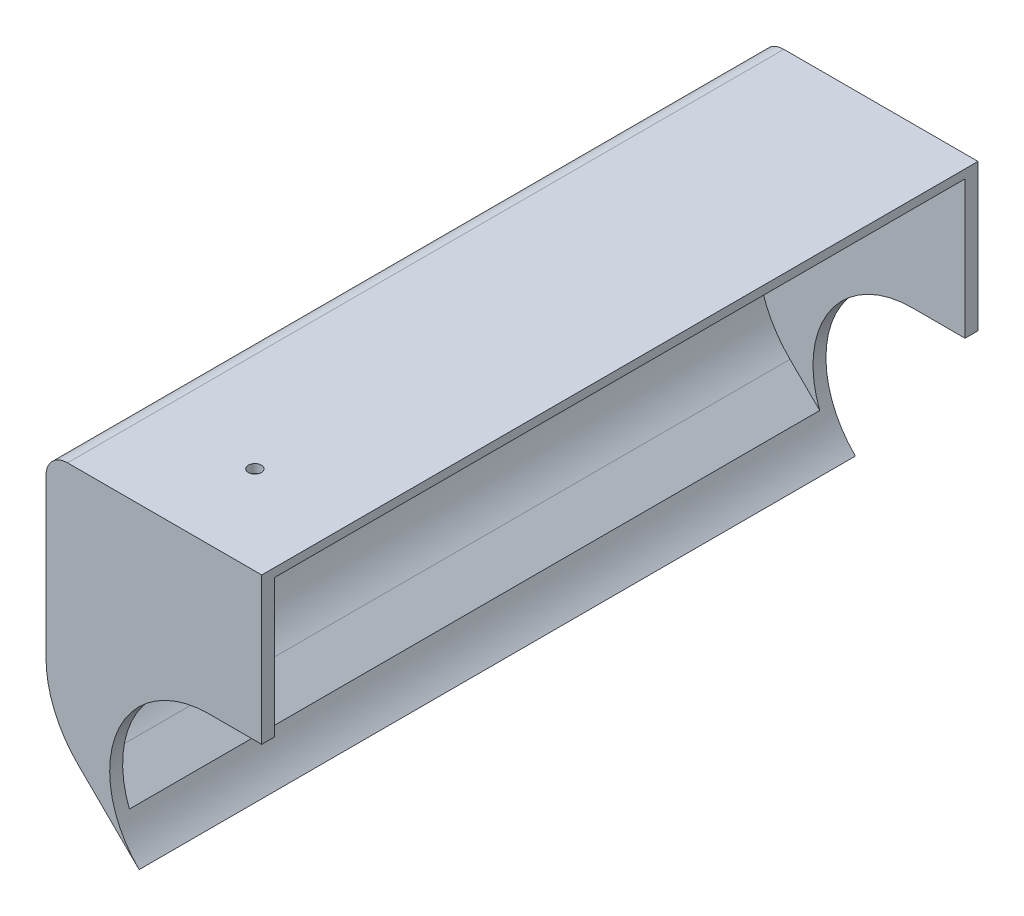
SolidWorks part; units mm, degrees
ref_plane "Front Plane" through (0, 0, 0) normal (0, 0, 1) x (1, 0, 0)
ref_plane "Top Plane" through (0, 0, 0) normal (0, 1, 0) x (1, 0, 0)
ref_plane "Right Plane" through (0, 0, 0) normal (1, 0, 0) x (0, 0, -1)
sketch "Sketch1" plane through (0, 0, 0) normal (0, 0, 1) x (1, 0, 0)
  line L0 (-176.4226, 3.6462) -> (-198.0073, 24.9918)
  line L1 (-198.0073, 24.9918) -> (-198.0073, 77)
  line L2 (-198.0073, 77) -> (-148.0073, 77)
  line L4 (-160.25, 43) -> (-148.0073, 43)
  line L6 (-148.0073, 43) -> (-148.0073, 77)
  arc A1 (-160.25, 43) -> (-176.4226, 3.6462) centre (-160.25, 20) ccw
extrude "Boss-Extrude1" add sketch "Sketch1" against normal blind 3
sketch "Sketch2" plane through (0, 0, -166) normal (0, 0, -1) x (-1, 0, 0)
  line L5 (198.0073, 24.9918) -> (198.0073, 77)
  line L6 (198.0073, 77) -> (148.0073, 77)
  line L7 (148.0073, 77) -> (148.0073, 43)
  line L8 (148.0073, 43) -> (160.25, 43)
  line L9 (176.4226, 3.6462) -> (198.0073, 24.9918)
  line L10 (198.0073, 24.9918) -> (198.0073, 77)
  line L11 (198.0073, 77) -> (148.0073, 77)
  line L12 (148.0073, 77) -> (148.0073, 43)
  line L13 (148.0073, 43) -> (160.25, 43)
  line L14 (176.4226, 3.6462) -> (198.0073, 24.9918)
  arc A1 (176.4226, 3.6462) -> (160.25, 43) centre (160.25, 20) ccw
  arc A2 (176.4226, 3.6462) -> (160.25, 43) centre (160.25, 20) ccw
  dimension "D1" = 0
extrude "Boss-Extrude2" add sketch "Sketch2" against normal blind 3 separate body
sketch "Sketch3" plane through (0, 0, -3) normal (0, 0, -1) x (-1, 0, 0)
  line L0 (181.6864, 11.6645) -> (196.0073, 25.8268)
  line L1 (196.0073, 25.8268) -> (196.0073, 75)
  line L2 (196.0073, 75) -> (148.0073, 75)
  line L3 (148.0073, 77) -> (148.0073, 75)
  line L4 (175.0163, 5.0683) -> (196.0073, 25.8268) construction
  line L5 (198.0073, 24.9918) -> (198.0073, 77)
  line L6 (198.0073, 77) -> (148.0073, 77)
  line L7 (148.0073, 77) -> (148.0073, 43)
  line L8 (148.0073, 43) -> (160.25, 43)
  line L9 (176.4226, 3.6462) -> (198.0073, 24.9918)
  line L10 (198.0073, 24.9918) -> (198.0073, 77)
  line L11 (198.0073, 77) -> (148.0073, 77)
  line L14 (176.4226, 3.6462) -> (198.0073, 24.9918)
  arc A0 (160.25, -3) -> (160.25, 43) centre (160.25, 20) ccw construction
  arc A1 (176.4226, 3.6462) -> (160.25, 43) centre (160.25, 20) ccw
  arc A3 (176.4226, 3.6462) -> (181.6864, 11.6645) centre (160.25, 20) ccw
  dimension "D1" = 0
  dimension "D2" = 2
extrude "Boss-Extrude3" add sketch "Sketch3" along normal up to surface (160 mm away) up to face at (-173.6482, 45.6762, -163)
fillet "Fillet1" radius 5 2 edges at (-198.0073, 77, -83) (-196.0073, 75, -83)
fillet "Fillet2" radius 25 2 edges at (-196.0073, 25.8268, -83) (-198.0073, 24.9918, -83)
sketch "Sketch4" plane through (-198.0073, 0, 0) normal (-1, 0, 0) x (0, 0, 1)
  line L0 (-166, 57) -> (0, 57) construction
  line L3 (-95.5, 57) -> (-70.5, 57) construction
  line L4 (-83, 57) -> (-83, 76.9624) construction
  circle A0 centre (-30, 47) radius 2.5
  circle A1 centre (-136, 47) radius 2.5
  circle A2 centre (-95.5, 57) radius 8.75
  circle A3 centre (-70.5, 57) radius 8.75
  dimension "D1" = 25
  dimension "D2" = 17.5
  dimension "D3" = 17.5
extrude "Cut-Extrude1" cut sketch "Sketch4" against normal blind 7
sketch "Sketch5" plane through (-196.0073, 0, 0) normal (1, 0, 0) x (0, 0, -1)
  line L4 (105.5, 67) -> (60.5, 67)
  line L5 (60.5, 67) -> (60.5, 47)
  line L6 (60.5, 47) -> (105.5, 47)
  line L7 (105.5, 47) -> (105.5, 67)
  line L8 (105.5, 67) -> (60.5, 67)
  line L9 (60.5, 67) -> (60.5, 47)
  line L10 (60.5, 47) -> (105.5, 47)
  line L11 (105.5, 47) -> (105.5, 67)
  circle A0 centre (70.5, 57) radius 8.75 construction
  circle A1 centre (70.5, 57) radius 8.75
  circle A2 centre (95.5, 57) radius 8.75 construction
  circle A3 centre (95.5, 57) radius 8.75
  dimension "D1" = 0
extrude "Boss-Extrude4" add sketch "Sketch5" along normal blind 8
sketch "Sketch6" plane through (-196.0073, 0, 0) normal (1, 0, 0) x (0, 0, -1)
  circle A0 centre (20.5, 60.4) radius 6
extrude "Cut-Extrude2" cut sketch "Sketch6" against normal up to surface (2 mm away) up to face at (-198.0073, 47, -27.5)
sketch "Sketch7" plane through (0, 77, 0) normal (0, 1, 0) x (1, 0, 0)
  circle A0 centre (-170.1073, 20.5) radius 1.5 construction
  circle A1 centre (-170.1073, 20.5) radius 1.5
extrude "Cut-Extrude3" cut sketch "Sketch7" against normal blind 3
